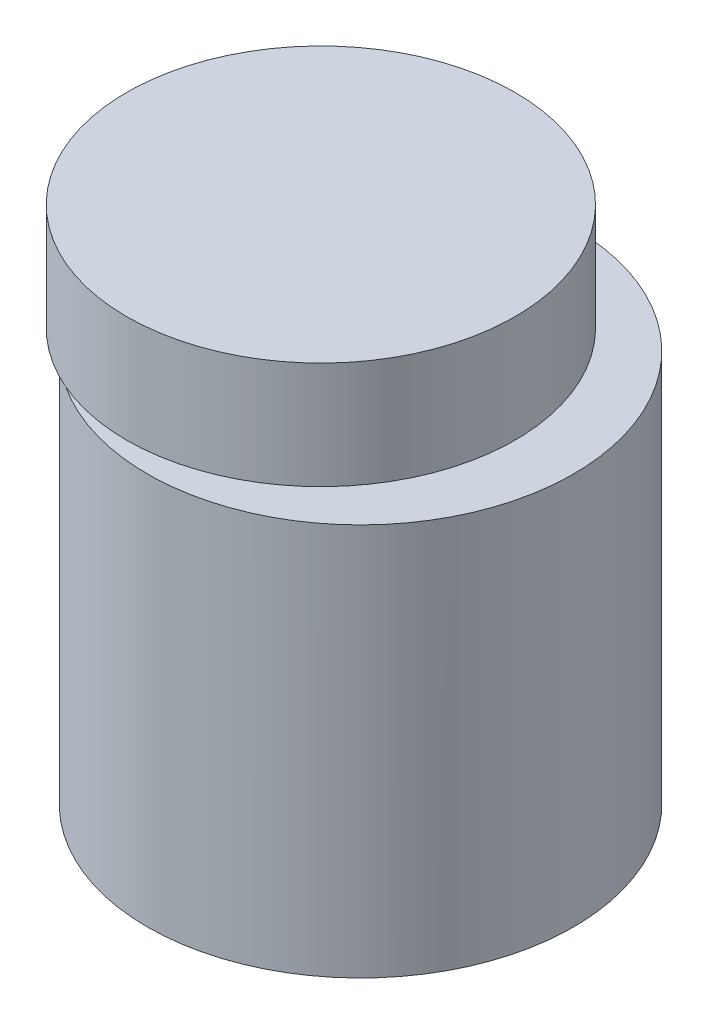
SolidWorks part; units mm, degrees
ref_plane "Ebene vorne" through (0, 0, 0) normal (0, 0, 1) x (1, 0, 0)
ref_plane "Ebene oben" through (0, 0, 0) normal (0, 1, 0) x (1, 0, 0)
ref_plane "Ebene rechts" through (0, 0, 0) normal (1, 0, 0) x (0, 0, -1)
sketch "Skizze1" plane through (0, 0, 0) normal (0, 1, 0) x (1, 0, 0)
  circle A0 centre (0, 0) radius 5.375
  dimension "D1" = 10.75
extrude "Aufsatz-Linear austragen1" add sketch "Skizze1" along normal blind 10
sketch "Skizze2" plane through (0, 0, 0) normal (0, -1, 0) x (-1, 0, 0)
  line L0 (1, -5.2812) -> (1, 5.2812)
  line L1 (-5.375, 0) -> (5.375, 0)
  circle A0 centre (0, 0) radius 5.375 construction
  dimension "D1" = 0
  dimension "D2" = 1
sketch "Skizze3" plane through (0, 0, 0) normal (0, -1, 0) x (-1, 0, 0)
  circle A0 centre (2, 0) radius 5.4
  point P1 (0, 0)
  dimension "D1" = 10.8
  dimension "D2" = 2
extrude "Aufsatz-Linear austragen3" add sketch "Skizze3" along normal blind 10
sketch "Skizze5" plane through (0, -10, 0) normal (0, -1, 0) x (1, 0, 0)
  circle A0 centre (-1, 0) radius 5.4
  circle A1 centre (-2, 0) radius 5.4 construction
  dimension "D2" = 1
  dimension "D3" = 10.8
extrude "Aufsatz-Linear austragen4" add sketch "Skizze5" along normal blind 7.9
sketch "Skizze6" plane through (0, 10, 0) normal (0, 1, 0) x (1, 0, 0)
  circle A1 centre (-1, 0) radius 4.9
  dimension "D1" = 9.8
  dimension "D2" = 1
extrude "Aufsatz-Linear austragen5" add sketch "Skizze6" along normal blind 2.7
sketch "Skizze8" plane through (0, -17.9, 0) normal (0, -1, 0) x (1, 0, 0)
  circle A0 centre (-1, 0) radius 2.6
  circle A1 centre (-1, 0) radius 5.4 construction
  dimension "D1" = 5.2
extrude "Schnitt-Linear austragen1" cut sketch "Skizze8" against normal blind 25 contours A0
sketch "Skizze9" plane through (0, 7.1, 0) normal (0, -1, 0) x (-1, 0, 0)
  line L1 (-1.05, -1.5992) -> (-1.6, -1.5992)
  line L2 (-1.05, -1.5992) -> (-1.05, 1.5998)
  line L3 (-1.05, 1.5998) -> (-1.6, 1.5998)
  line L4 (-1.6, -1.5992) -> (-1.6, 1.5998)
  circle A0 centre (1, 0) radius 2.6 construction
  dimension "D2" = 2.6
  dimension "D1" = 0.55
extrude "Aufsatz-Linear austragen6" add sketch "Skizze9" along normal blind 15
ref_axis "Achse1" through (-1, 40.5876, 0) along (0, -1, 0)
sketch "Skizze10" plane through (0, -17.9, 0) normal (0, -1, 0) x (1, 0, 0)
  line L1 (-10.4292, 7.7406) -> (10.3859, 7.7406)
  line L2 (-10.4292, 7.7406) -> (-10.4292, -7.8707)
  line L3 (-10.4292, -7.8707) -> (10.3859, -7.8707)
  line L4 (10.3859, 7.7406) -> (10.3859, -7.8707)
extrude "Schnitt-Linear austragen2" cut sketch "Skizze10" against normal blind 18
